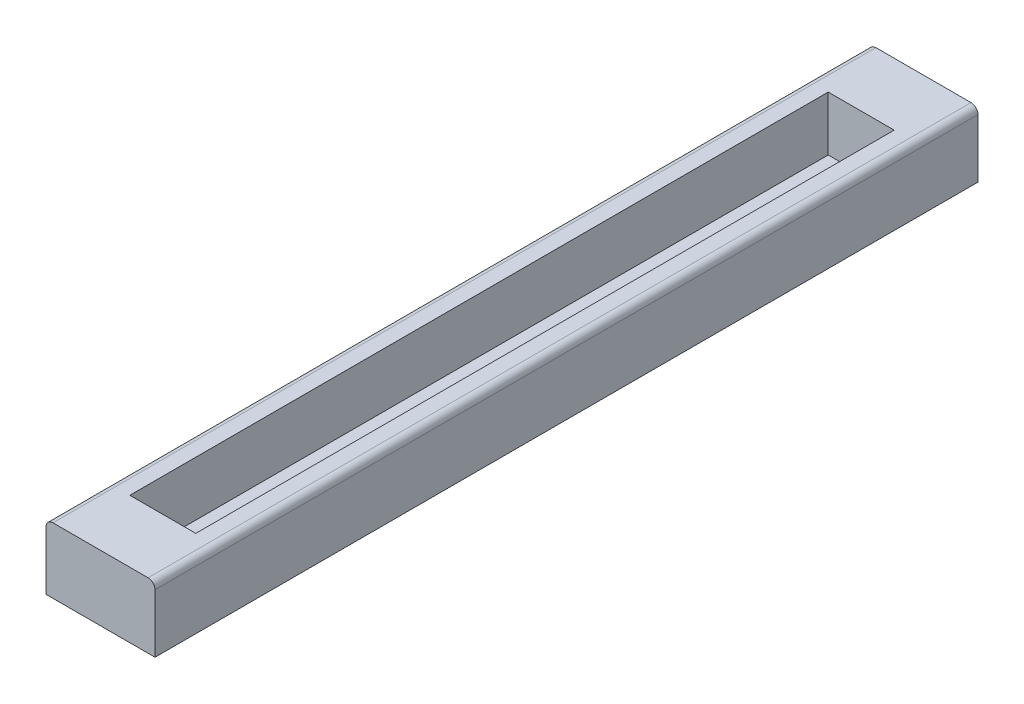
SolidWorks part; units mm, degrees
ref_plane "Front Plane" through (0, 0, 0) normal (0, 0, 1) x (1, 0, 0)
ref_plane "Top Plane" through (0, 0, 0) normal (0, 1, 0) x (1, 0, 0)
ref_plane "Right Plane" through (0, 0, 0) normal (1, 0, 0) x (0, 0, -1)
ref_plane "Plane1" through (0, 1.2, 0) normal (0, 1, 0) x (-1, 0, 0)
sketch "Sketch1" plane through (0, 1.2, 0) normal (0, 1, 0) x (-1, 0, 0)
  line L0 (-1, -7.55) -> (1, -7.55)
  line L1 (1, -7.55) -> (1, 7.55)
  line L2 (1, 7.55) -> (-1, 7.55)
  line L3 (-1, 7.55) -> (-1, -7.55)
extrude "Boss-Extrude1" add sketch "Sketch1" against normal blind 1.2
sketch "Sketch2" plane through (0, 1.2, 0) normal (0, 1, 0) x (-1, 0, 0)
  line L0 (-0.605, -6.407) -> (0.605, -6.407)
  line L1 (0.605, -6.407) -> (0.605, 6.407)
  line L2 (0.605, 6.407) -> (-0.605, 6.407)
  line L3 (-0.605, 6.407) -> (-0.605, -6.407)
extrude "Cut-Extrude1" cut sketch "Sketch2" against normal blind 1
fillet "Fillet1" radius 0.127 2 edges at (1, 1.2, 0) (-1, 1.2, 0) tangent propagation no
